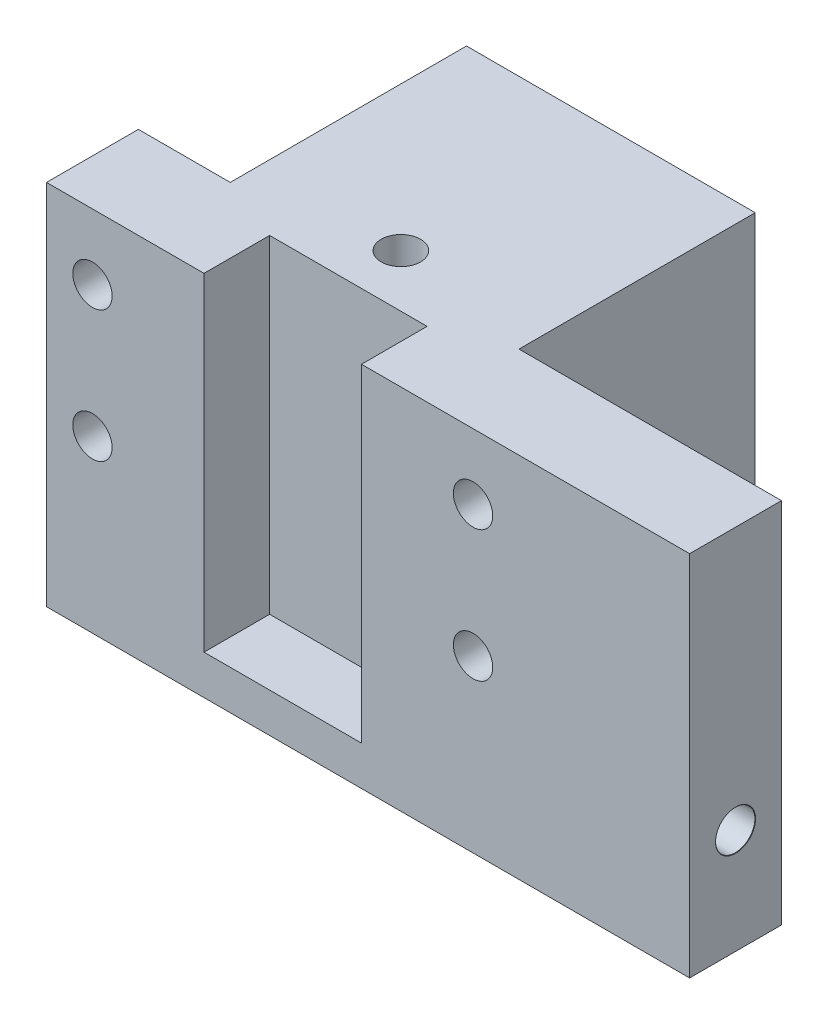
SolidWorks part; units mm, degrees
ref_plane "Front Plane" through (0, 0, 0) normal (0, 0, 1) x (1, 0, 0)
ref_plane "Top Plane" through (0, 0, 0) normal (0, 1, 0) x (1, 0, 0)
ref_plane "Right Plane" through (0, 0, 0) normal (1, 0, 0) x (0, 0, -1)
sketch "Sketch1" plane through (0, 0, 0) normal (0, 1, 0) x (1, 0, 0)
  line L1 (-10.5256, 12.3096) -> (38.4744, 12.3096)
  line L2 (-10.5256, 12.3096) -> (-10.5256, -12.6904)
  line L3 (-10.5256, -12.6904) -> (38.4744, -12.6904)
  line L4 (38.4744, 12.3096) -> (38.4744, -12.6904)
  dimension "D1" = 25
  dimension "D2" = 49
extrude "Boss-Extrude1" add sketch "Sketch1" along normal blind 28
sketch "Sketch2" plane through (0, 28, 0) normal (0, 1, 0) x (1, 0, 0)
  line L0 (-10.5256, -12.6904) -> (38.4744, -12.6904) construction
  line L1 (1.4744, -12.6904) -> (13.4744, -12.6904)
  line L2 (1.4744, -12.6904) -> (1.4744, -7.6904)
  line L3 (1.4744, -7.6904) -> (13.4744, -7.6904)
  line L4 (13.4744, -12.6904) -> (13.4744, -7.6904)
  line L5 (-10.5256, 12.3096) -> (-10.5256, -12.6904) construction
  dimension "D1" = 12
  dimension "D2" = 12
  dimension "D3" = 5
extrude "Cut-Extrude1" cut sketch "Sketch2" against normal blind 25
hole_wizard "Ø3.0mm Dowel Hole1" positions "Sketch3" profile "Sketch4" hole size "Ø3.0" standard "ANSI Metric"
sketch "Sketch3" plane through (0, 0, -12.3096) normal (0, 0, -1) x (-1, 0, 0)
  line L0 (-38.4744, 28) -> (-38.4744, 0) construction
  line L3 (-38.4744, 0) -> (10.5256, 0) construction
  point P0 (-7.4744, 16)
  point P10 (-12.8465, 27.7)
  dimension "D1" = 31
  dimension "D2" = 16
sketch "Sketch4" plane through (7.4744, 16, -12.3096) normal (1, 0, 0) x (0, 1, 0)
  line L0 (0, 0) -> (0, 12)
  line L1 (0, 12) -> (1.5, 11.0987)
  line L2 (1.5, 11.0987) -> (1.5, 0.025)
  line L3 (1.5, 0.025) -> (1.525, 0)
  line L5 (1.525, 0) -> (0, 0)
  line L6 (-1.5, 0.025) -> (-1.525, 0) construction
  line L10 (0, 12) -> (-1.5, 11.0987) construction
  line L11 (0, -6.35) -> (0, 107.95) construction
  dimension "Hole Dia." = 3
  dimension "Hole Depth" = 12
  dimension "Near C'Sink Dia." = 3.05
  dimension "Near C'Sink Angle" = 90
  dimension "Drill Angle" = 118
hole_wizard "Ø3.0mm Dowel Hole2" positions "Sketch7" profile "Sketch8" hole size "Ø3.0" standard "ANSI Metric" end condition up to next
sketch "Sketch7" plane through (38.4744, 0, 0) normal (1, 0, 0) x (0, 0, -1)
  line L0 (-12.6904, 0) -> (12.3096, 0) construction
  line L1 (12.3096, 28) -> (12.3096, 0) construction
  point P0 (-9.1904, 8)
  dimension "D1" = 8
  dimension "D2" = 21.5
sketch "Sketch8" plane through (38.4744, 8, 9.1904) normal (0, 1, 0) x (0, 0, -1)
  line L0 (0, 0) -> (0, 25)
  line L1 (0, 25) -> (1.5, 25)
  line L2 (1.5, 25) -> (1.5, 0.025)
  line L3 (1.5, 0.025) -> (1.525, 0)
  line L5 (1.525, 0) -> (0, 0)
  line L6 (-1.5, 0.025) -> (-1.525, 0) construction
  line L11 (0, -6.35) -> (0, 107.95) construction
  dimension "Thru Hole Dia." = 3
  dimension "Thru Hole Depth" = 25
  dimension "Near C'Sink Dia." = 3.05
  dimension "Near C'Sink Angle" = 90
hole_wizard "Ø3.0mm Dowel Hole3" positions "Sketch9" profile "Sketch10" hole size "Ø3.0" standard "ANSI Metric" end condition through all
sketch "Sketch9" plane through (0, 0, 0) normal (0, -1, 0) x (-1, 0, 0)
  line L1 (-38.4744, 12.3096) -> (10.5256, 12.3096) construction
  line L3 (-38.4744, -12.6904) -> (-38.4744, 12.3096) construction
  point P0 (-7.4744, -3.6904)
  dimension "D1" = 31
  dimension "D2" = 16
sketch "Sketch10" plane through (7.4744, 0, 3.6904) normal (1, 0, 0) x (0, 0, -1)
  line L0 (0, 0) -> (0, 28)
  line L1 (0, 28) -> (1.5, 28)
  line L2 (1.5, 28) -> (1.5, 0.025)
  line L3 (1.5, 0.025) -> (1.525, 0)
  line L5 (1.525, 0) -> (0, 0)
  line L6 (-1.5, 0.025) -> (-1.525, 0) construction
  line L11 (0, -6.35) -> (0, 107.95) construction
  dimension "Thru Hole Dia." = 3
  dimension "Thru Hole Depth" = 28
  dimension "Near C'Sink Dia." = 3.05
  dimension "Near C'Sink Angle" = 90
sketch "Sketch13" plane through (0, 0, 12.6904) normal (0, 0, 1) x (1, 0, 0)
  line L0 (-10.5256, 28) -> (1.4744, 28) construction
  line L1 (13.4744, 28) -> (38.4744, 28) construction
  line L6 (-10.5256, 28) -> (-10.5256, 0) construction
  line L7 (13.4744, 3) -> (13.4739, 8) construction
  line L8 (13.4744, 3) -> (13.4744, 28) construction
  circle A0 centre (-7.0256, 23) radius 1.5
  circle A3 centre (-7.0256, 13) radius 1.5
  circle A4 centre (21.9724, 23) radius 1.5
  circle A5 centre (21.9744, 13) radius 1.5
  point P2 (0, 0)
  point P5 (-7.8298, 14.3279)
  point P6 (0, 0)
  point P9 (9.5043, 23.4166)
  point P12 (8.9889, 14.3279)
  point P13 (8.9889, 24.0725)
  point P20 (0, 0)
  point P23 (0, 0)
  point P26 (0, 0)
  point P27 (0, 0)
  point P28 (0, 0)
  dimension "D1" = 5
  dimension "D2" = 5
  dimension "D3" = 10
  dimension "D4" = 3.5
  dimension "D5" = 8.5
  dimension "D6" = 8.5
  dimension "D8" = 10
extrude "Cut-Extrude2" cut sketch "Sketch13" against normal blind 12
sketch "Sketch14" plane through (0, 28, 0) normal (0, 1, 0) x (1, 0, 0)
  line L0 (-10.5256, -12.6904) -> (1.4744, -12.6904) construction
  line L1 (-10.5256, 12.3096) -> (-3.5256, 12.3096)
  line L2 (-10.5256, 12.3096) -> (-10.5256, -5.6904)
  line L3 (-10.5256, -5.6904) -> (-3.5256, -5.6904)
  line L4 (-3.5256, 12.3096) -> (-3.5256, -5.6904)
  line L5 (1.4744, -7.6904) -> (1.4744, -12.6904) construction
  line L6 (13.4744, -12.6904) -> (38.4744, -12.6904) construction
  line L7 (18.4744, 12.3096) -> (38.4744, 12.3096)
  line L8 (18.4744, 12.3096) -> (18.4744, -5.6904)
  line L9 (18.4744, -5.6904) -> (38.4744, -5.6904)
  line L10 (38.4744, 12.3096) -> (38.4744, -5.6904)
  line L11 (13.4744, -12.6904) -> (13.4744, -7.6904) construction
  point P17 (34.4744, 12.3096)
  dimension "D1" = 7
  dimension "D2" = 5
  dimension "D3" = 7
  dimension "D4" = 5
extrude "Cut-Extrude3" cut sketch "Sketch14" against normal blind 28
